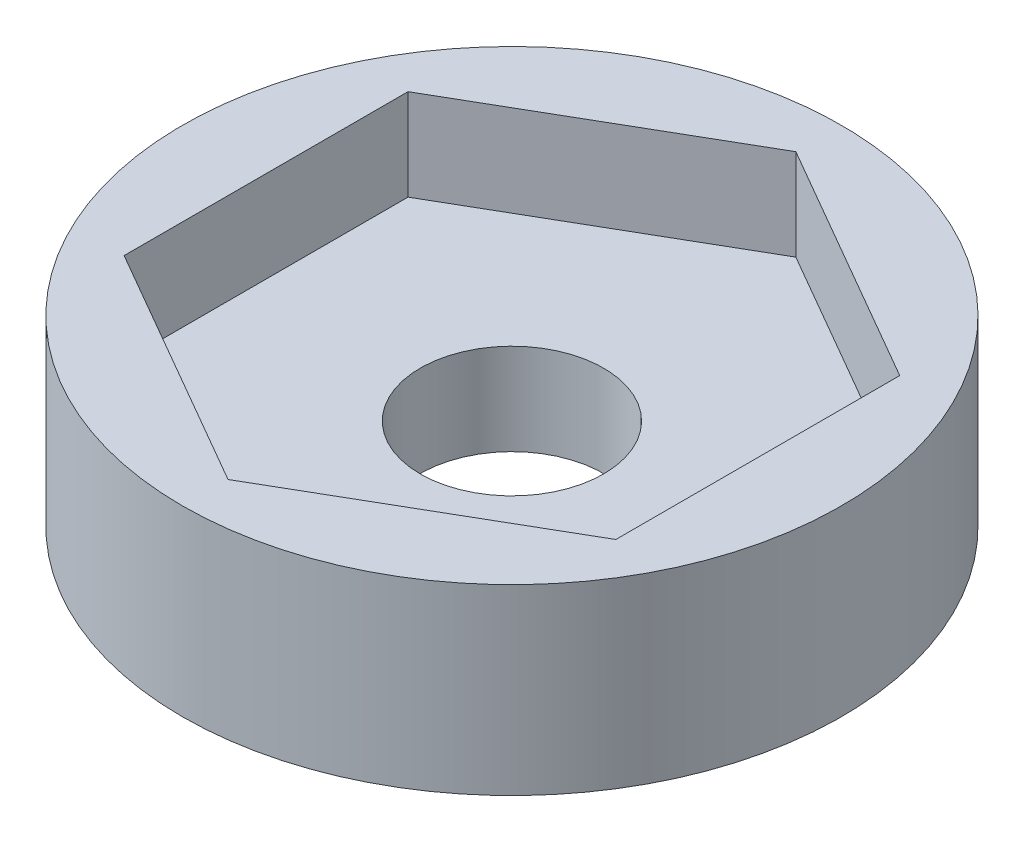
SolidWorks part; units mm, degrees
ref_plane "Front Plane" through (0, 0, 0) normal (0, 0, 1) x (1, 0, 0)
ref_plane "Top Plane" through (0, 0, 0) normal (0, 1, 0) x (1, 0, 0)
ref_plane "Right Plane" through (0, 0, 0) normal (1, 0, 0) x (0, 0, -1)
sketch "Sketch1" plane through (0, 0, 0) normal (0, 1, 0) x (1, 0, 0)
  line L0 (8.5471, -4.9347) -> (9.9219, -5.7284) construction
  line L1 (8.5471, 4.9347) -> (0, 9.8693)
  line L2 (0, 9.8693) -> (-8.5471, 4.9347)
  line L3 (-8.5471, 4.9347) -> (-8.5471, -4.9347)
  line L4 (-8.5471, -4.9347) -> (0, -9.8693)
  line L5 (0, -9.8693) -> (8.5471, -4.9347)
  line L6 (8.5471, -4.9347) -> (8.5471, 4.9347)
  circle A0 centre (0, 0) radius 8.5471 construction
  circle A1 centre (0, 0) radius 11.4568
  dimension "D1" = 17.0942
  dimension "D2" = 1.5875
extrude "Boss-Extrude1" add sketch "Sketch1" along normal blind 3.175
sketch "Sketch2" plane through (0, 0, 0) normal (0, 1, 0) x (1, 0, 0)
  circle A0 centre (0, 0) radius 11.4568
  circle A1 centre (0, 0) radius 3.1877
  circle A2 centre (0, 0) radius 11.4568 construction
  dimension "D1" = 6.3754
extrude "Boss-Extrude2" add sketch "Sketch2" against normal blind 3.175
sketch "Sketch3" plane through (0, -3.175, 0) normal (0, -1, 0) x (-1, 0, 0)
  circle A0 centre (0, 0) radius 11.4568
  circle A1 centre (0, 0) radius 11.4568 construction
  circle A2 centre (0, 0) radius 2.794
  dimension "D1" = 5.588
extrude "Boss-Extrude3" [suppressed] add sketch "Sketch3" along normal offset from surface (0.127 mm away) 3.175 from surface up to face at (0, -3.175, 3.1877) starting at plane "Top Plane"
sketch "Sketch4" plane through (0, 0, 0) normal (1, 0, 0) x (0, 0, -1)
  line L0 (11.4568, -3.175) -> (11.4568, 0)
  line L1 (11.4568, -3.175) -> (11.4568, 3.175) construction
  line L2 (11.4568, -3.175) -> (5.5689, -3.175)
  line L3 (-11.4568, -3.175) -> (11.4568, -3.175) construction
  line L4 (5.5689, -3.175) -> (5.5689, -0.635)
  line L5 (5.5689, -0.635) -> (11.22, -0.2534)
  line L6 (11.4568, -3.175) -> (11.4568, 3.175) construction
  line L7 (4.9347, 0) -> (9.8693, 0) construction
  line L8 (3.1877, -3.175) -> (3.1877, 0) construction
  line L9 (0, 0) -> (0, -3.175) construction
  arc A0 (11.4568, 0) -> (11.22, -0.2534) centre (11.2028, 0) cw
  dimension "D3" = 0.254
  dimension "D1" = 2.54
  dimension "D2" = 2.3813
revolve "Cut-Revolve1" [suppressed] cut sketch "Sketch4" angle 360 about L9
fillet "Fillet1" [suppressed] radius 2.54
